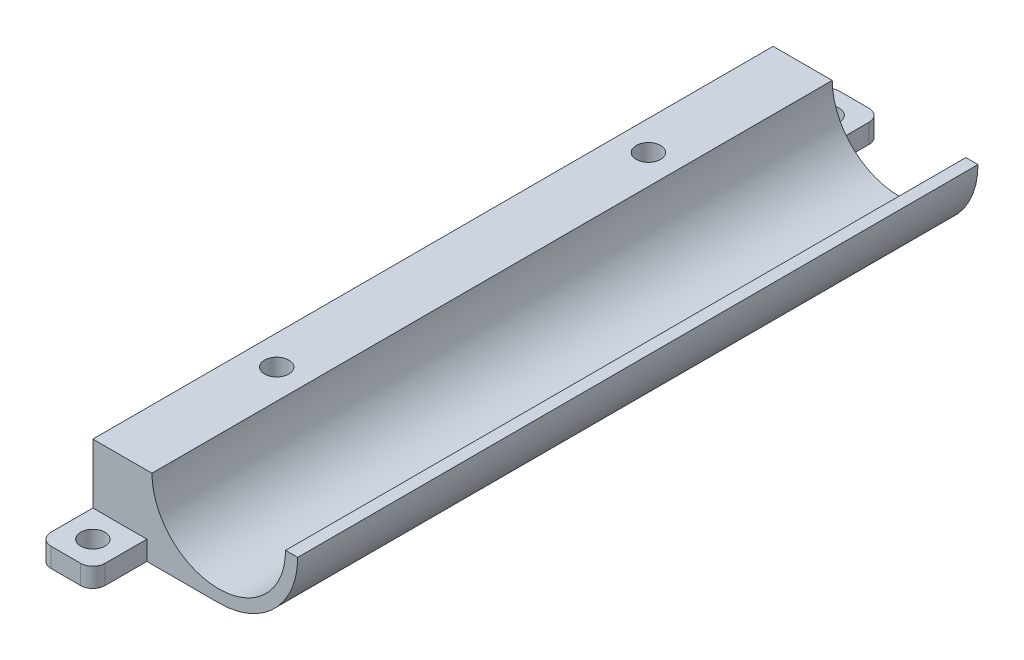
SolidWorks part; units mm, degrees
material "ABS"
ref_plane "X-Y Datum" through (0, 0, 0) normal (0, 0, 1) x (1, 0, 0)
ref_plane "X-Z Datum" through (0, 0, 0) normal (0, 1, 0) x (1, 0, 0)
ref_plane "Y-Z Datum" through (0, 0, 0) normal (1, 0, 0) x (0, 0, -1)
sketch "Sketch1" plane through (0, 0, 0) normal (0, 0, 1) x (1, 0, 0)
  line L0 (-13, 0) -> (-20.7245, 0)
  line L1 (-20.7245, 0) -> (-20.7245, -13)
  line L2 (-20.7245, -13) -> (0, -13)
  line L3 (-13, 0) -> (13, 0)
  circle A0 centre (0, 0) radius 13
  circle A1 centre (0, 0) radius 11
  dimension "D3" = 2
  dimension "D2" = 22
  dimension "D1" = 7.7245
extrude "Boss-Extrude1" add sketch "Sketch1" along normal blind 112 contours A0 L0 L1 L2 | A1 L3 A0 region at (-15.067, -7.4542, 0) region at (-12, -0.2907, 0)
sketch "Sketch2" plane through (0, 0, 0) normal (0, 1, 0) x (1, 0, 0)
  line L0 (-15.8622, 0) -> (-15.8622, -112) construction
  line L1 (-11, 0) -> (-20.7245, 0) construction
  line L2 (-11, -112) -> (-20.7245, -112) construction
  line L3 (-15.8622, 0) -> (-15.8622, -25.4) construction
  line L4 (-15.8622, -112) -> (-15.8622, -86.6) construction
  circle A0 centre (-15.8622, -25.4) radius 2
  circle A1 centre (-15.8622, -86.6) radius 2
  dimension "D2" = 4
  dimension "D4" = 4
  dimension "D1" = 25.4
  dimension "D3" = 25.4
extrude "Cut-Extrude1" cut sketch "Sketch2" against normal blind 5
sketch "Sketch3" plane through (0, -13, 0) normal (0, -1, 0) x (1, 0, 0)
  line L0 (-16.2795, 112) -> (-16.2795, 120.89) construction
  line L1 (-20.7245, 112) -> (-11.8345, 112)
  line L2 (-20.7245, 112) -> (-20.7245, 120.89)
  line L3 (-20.7245, 120.89) -> (-11.8345, 120.89)
  line L4 (-11.8345, 112) -> (-11.8345, 120.89)
  line L5 (-20.7245, 56) -> (13, 56) construction
  line L6 (-20.7245, 112) -> (-20.7245, 0) construction
  line L7 (13, 112) -> (13, 0) construction
  line L8 (-20.7245, 112) -> (-20.7245, 120.89)
  line L9 (-11.8345, 112) -> (-11.8345, 120.89)
  line L10 (-16.2795, 0) -> (-16.2795, -8.89) construction
  line L11 (-11.8345, 0) -> (-11.8345, -8.89)
  line L12 (-20.7245, 0) -> (-20.7245, -8.89)
  line L13 (-11.8345, 0) -> (-11.8345, -8.89)
  line L14 (-20.7245, -8.89) -> (-11.8345, -8.89)
  line L15 (-20.7245, 0) -> (-20.7245, -8.89)
  line L16 (-20.7245, 0) -> (-11.8345, 0)
  circle A0 centre (-16.2795, 116.445) radius 2
  circle A1 centre (-16.2795, -4.445) radius 2
  line M3 (-20.7245, 0) -> (0, 0)
  line M5 (0, 112) -> (-20.7245, 112)
  dimension "D1" = 4
  dimension "D2" = 8.89
  dimension "D3" = 8.89
extrude "Boss-Extrude2" add sketch "Sketch3" against normal blind 3.175 contours L4 L3 L2 A0 M5 | L12 L14 L11 A1 M3 region at (-20.5987, -13, 116.445) region at (-11.9602, -13, -4.445)
fillet "Fillet1" radius 2 4 edges at (-20.7245, -11.4125, 120.89) (-11.8345, -11.4125, 120.89) (-11.8345, -11.4125, -8.89) (-20.7245, -11.4125, -8.89)
